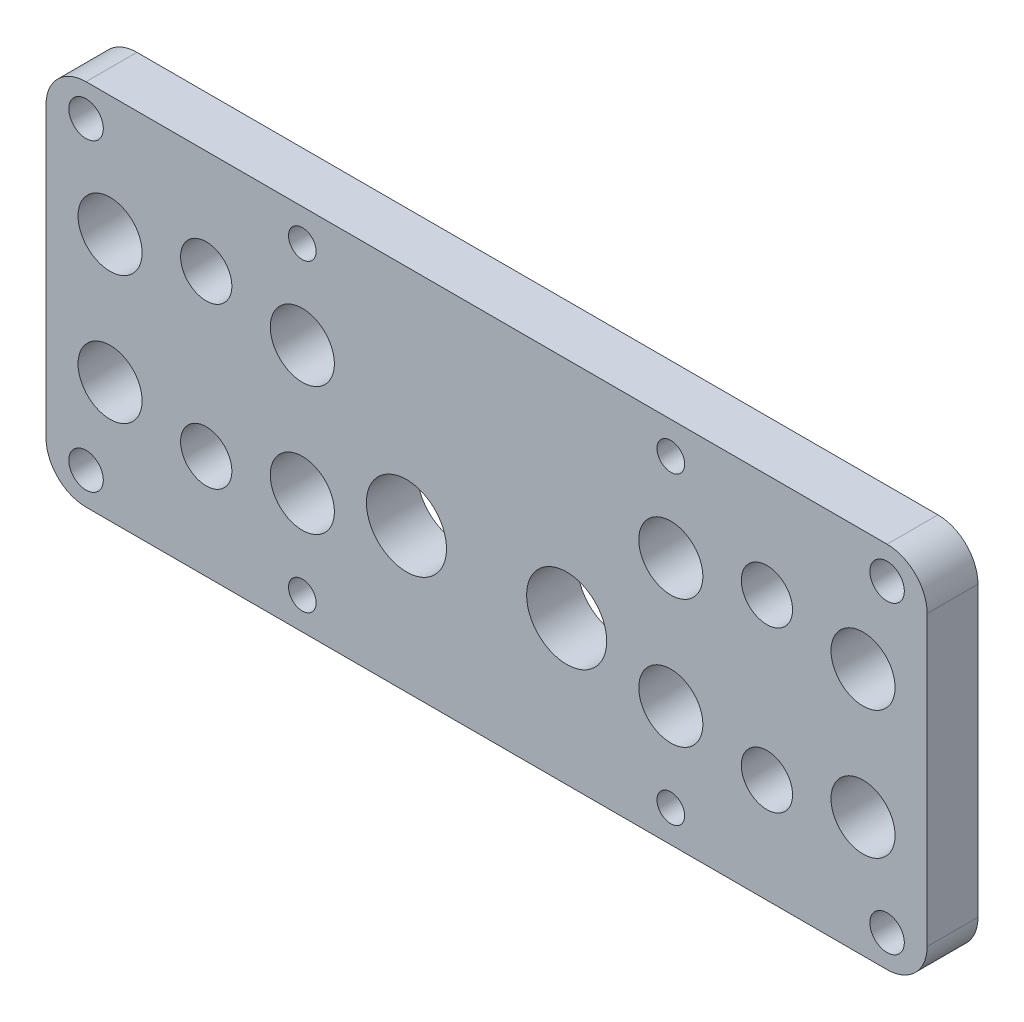
SolidWorks part; units mm, degrees
ref_plane "Front Plane" through (0, 0, 0) normal (0, 0, 1) x (1, 0, 0)
ref_plane "Top Plane" through (0, 0, 0) normal (0, 1, 0) x (1, 0, 0)
ref_plane "Right Plane" through (0, 0, 0) normal (1, 0, 0) x (0, 0, -1)
sketch "Sketch1" plane through (0, 0, 0) normal (0, 0, 1) x (1, 0, 0)
  line L0 (-55, -23) -> (-55, 23)
  line L1 (-55, -23) -> (55, -23)
  line L2 (-55, 23) -> (55, 23)
  line L3 (55, -23) -> (55, 23)
  line L4 (-55, -23) -> (55, 23) construction
  line L5 (-55, 23) -> (55, -23) construction
  point P1 (0, 0)
  dimension "D1" = 110
  dimension "D2" = 46
extrude "Boss-Extrude1" add sketch "Sketch1" along normal blind 6.35
sketch "Sketch2" plane through (0, 0, 0) normal (0, 0, -1) x (-1, 0, 0)
  line L0 (-35, -10) -> (-35, 10) construction
  line L1 (-35, -10) -> (35, -10) construction
  line L2 (-35, 10) -> (35, 10) construction
  line L3 (35, -10) -> (35, 10) construction
  line L4 (-35, -10) -> (35, 10) construction
  line L5 (-35, 10) -> (35, -10) construction
  point P1 (0, 0)
  dimension "D1" = 70
  dimension "D2" = 20
hole_wizard "M6 Clearance Hole1" positions "Sketch4" profile "Sketch3" hole size "M6" standard "ANSI Metric" end condition through all
sketch "Sketch4" plane through (0, 0, 0) normal (0, 0, -1) x (-1, 0, 0)
  point P0 (-35, 10)
  point P3 (-35, -10)
  point P6 (35, -10)
  point P9 (35, 10)
sketch "Sketch3" plane through (35, 10, 0) normal (1, 0, 0) x (0, 1, 0)
  line L0 (0, 0) -> (0, 6.35)
  line L1 (0, 6.35) -> (3.2, 6.35)
  line L2 (3.2, 6.35) -> (3.2, 0)
  line L5 (3.2, 0) -> (0, 0)
  line L11 (0, -6.35) -> (0, 107.95) construction
  dimension "Thru Hole Dia." = 6.4
  dimension "Thru Hole Depth" = 6.35
sketch "Sketch5" plane through (0, 0, 0) normal (0, 0, -1) x (-1, 0, 0)
  line L0 (-10, -5) -> (10, -5) construction
  circle A0 centre (-10, -5) radius 5
  circle A1 centre (10, -5) radius 5
  point P4 (0, -5)
  dimension "D2" = 10
  dimension "D3" = 10
  dimension "D1" = 20
  dimension "D4" = 5
extrude "Cut-Extrude1" cut sketch "Sketch5" against normal through all
sketch "Sketch7" plane through (0, 0, 0) normal (0, 0, -1) x (-1, 0, 0)
  line L1 (-23, -8) -> (23, -8) construction
  line L2 (-23, -8) -> (-23, 8) construction
  line L3 (-23, 8) -> (23, 8) construction
  line L4 (23, -8) -> (23, 8) construction
  line L5 (-23, -8) -> (23, 8) construction
  line L6 (-23, 8) -> (23, -8) construction
  line L7 (-47, -8) -> (-23, -8) construction
  line L8 (-47, -8) -> (-47, 8) construction
  line L9 (-47, 8) -> (-23, 8) construction
  line L10 (-23, -8) -> (-23, 8) construction
  line L11 (-47, -8) -> (-23, 8) construction
  line L12 (-47, 8) -> (-23, -8) construction
  line L13 (23, -8) -> (47, -8) construction
  line L14 (23, -8) -> (23, 8) construction
  line L15 (23, 8) -> (47, 8) construction
  line L16 (47, -8) -> (47, 8) construction
  line L17 (23, -8) -> (47, 8) construction
  line L18 (23, 8) -> (47, -8) construction
  circle A0 centre (-23, 8) radius 4
  circle A1 centre (-23, -8) radius 4
  circle A2 centre (23, -8) radius 4
  circle A3 centre (23, 8) radius 4
  circle A4 centre (-47, 8) radius 4
  circle A5 centre (-47, -8) radius 4
  circle A6 centre (47, 8) radius 4
  circle A7 centre (47, -8) radius 4
  point P0 (0, 0)
  point P10 (-35, 0)
  point P15 (35, 0)
  dimension "D3" = 8
  dimension "D1" = 46
  dimension "D2" = 16
  dimension "D4" = 24
  dimension "D5" = 24
extrude "Cut-Extrude2" cut sketch "Sketch7" against normal through all
sketch "Sketch8" plane through (0, 0, 0) normal (0, 0, -1) x (-1, 0, 0)
  line L1 (-23, -19) -> (23, -19) construction
  line L2 (-23, -19) -> (-23, 19) construction
  line L3 (-23, 19) -> (23, 19) construction
  line L4 (23, -19) -> (23, 19) construction
  line L5 (-23, -19) -> (23, 19) construction
  line L6 (-23, 19) -> (23, -19) construction
  line L7 (-50, -19) -> (50, -19) construction
  line L8 (-50, -19) -> (-50, 19) construction
  line L9 (-50, 19) -> (50, 19) construction
  line L10 (50, -19) -> (50, 19) construction
  line L11 (-50, -19) -> (50, 19) construction
  line L12 (-50, 19) -> (50, -19) construction
  point P0 (0, 0)
  point P6 (0, 0)
  dimension "D1" = 38
  dimension "D2" = 46
  dimension "D3" = 38
  dimension "D4" = 100
fillet "Fillet1" radius 5 4 edges at (-55, 23, 3.175) (-55, -23, 3.175) (55, -23, 3.175) (55, 23, 3.175)
hole_wizard "#8-32 Tapped Hole1" positions "Sketch10" profile "Sketch9" tap size "#8-32" standard "ANSI Inch" end condition through all
sketch "Sketch10" plane through (0, 0, 0) normal (0, 0, -1) x (-1, 0, 0)
  point P0 (-23, 19)
  point P3 (23, 19)
  point P6 (23, -19)
  point P9 (-23, -19)
sketch "Sketch9" plane through (23, 19, 0) normal (1, 0, 0) x (0, 1, 0)
  line L0 (0, 0) -> (0, 6.35)
  line L1 (0, 6.35) -> (1.7272, 6.35)
  line L2 (1.7272, 6.35) -> (1.7272, 0)
  line L5 (1.7272, 0) -> (0, 0)
  line L11 (0, -6.35) -> (0, 107.95) construction
  dimension "Thru Tap Drill Dia." = 3.4544
  dimension "Thru Tap Drill Depth" = 6.35
cosmetic thread "Hole Thread1" parameters "D2"=4.1656
cosmetic thread "Hole Thread2" parameters "D2"=4.1656
cosmetic thread "Hole Thread3" parameters "D2"=4.1656
cosmetic thread "Hole Thread4" parameters "D2"=4.1656
hole_wizard "#8 Clearance Hole1" positions "Sketch12" profile "Sketch11" hole size "#8" standard "ANSI Inch" end condition through all
sketch "Sketch12" plane through (0, 0, 0) normal (0, 0, -1) x (-1, 0, 0)
  point P0 (-50, 19)
  point P3 (-50, -19)
  point P6 (50, -19)
  point P9 (50, 19)
sketch "Sketch11" plane through (50, 19, 0) normal (1, 0, 0) x (0, 1, 0)
  line L0 (0, 0) -> (0, 6.35)
  line L1 (0, 6.35) -> (2.1526, 6.35)
  line L2 (2.1526, 6.35) -> (2.1526, 0)
  line L5 (2.1526, 0) -> (0, 0)
  line L11 (0, -6.35) -> (0, 107.95) construction
  dimension "Thru Hole Dia." = 4.3053
  dimension "Thru Hole Depth" = 6.35
